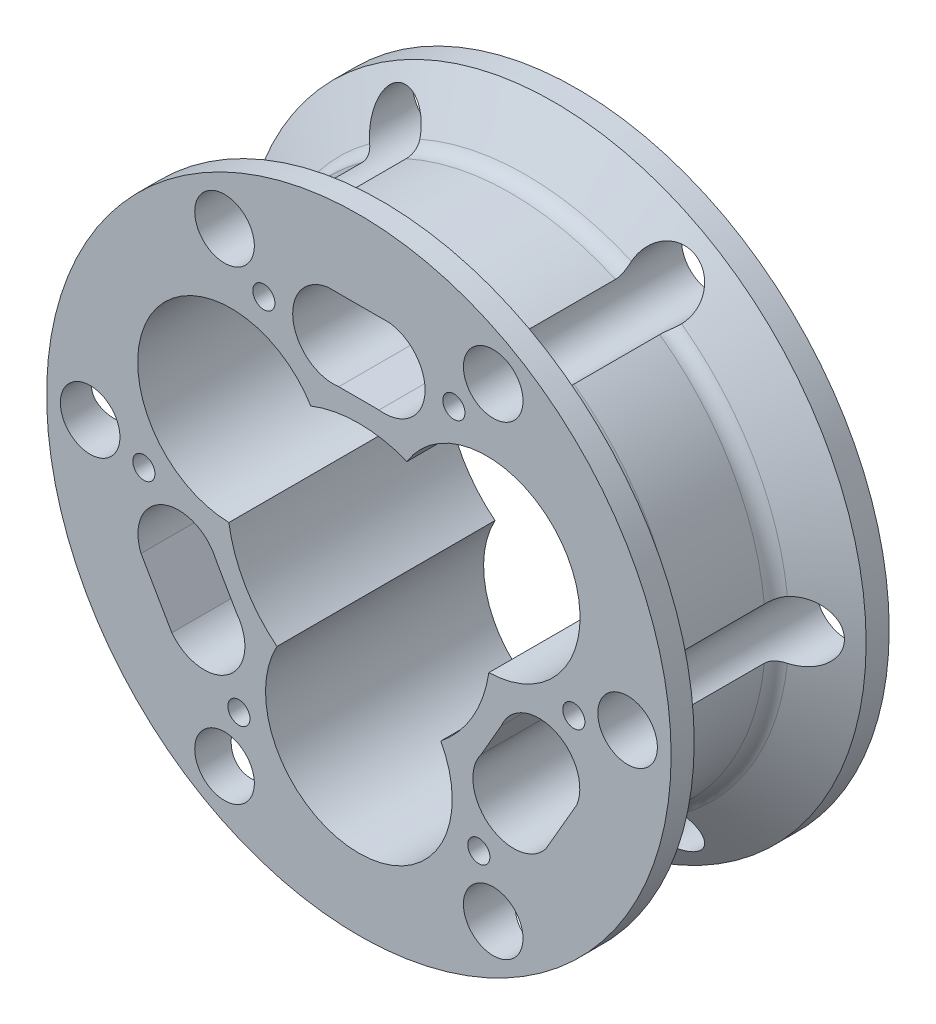
SolidWorks part; units mm, degrees
ref_plane "Front Plane" through (0, 0, 0) normal (0, 0, 1) x (1, 0, 0)
ref_plane "Top Plane" through (0, 0, 0) normal (0, 1, 0) x (1, 0, 0)
ref_plane "Right Plane" through (0, 0, 0) normal (1, 0, 0) x (0, 0, -1)
sketch "Sketch1" plane through (0, 0, 0) normal (0, 1, 0) x (1, 0, 0)
  line L0 (42.9895, 30.0228) -> (0, 30.0228)
  line L1 (0, 30.0228) -> (0, 0)
  line L2 (0, 0) -> (42.9895, 0)
  line L3 (42.9895, 0) -> (42.9895, 3.175)
  line L4 (42.9895, 3.175) -> (35.0774, 7.7431)
  line L5 (35.0774, 7.7431) -> (35.0774, 22.2797)
  line L6 (35.0774, 22.2797) -> (42.9895, 26.8478)
  line L7 (42.9895, 26.8478) -> (42.9895, 30.0228)
  line L8 (0, 30.0228) -> (0, 0) construction
revolve "Revolve1" add sketch "Sketch1" angle 360 about L8 reverse direction yes
sketch "Sketch2" plane through (0, 0, 0) normal (0, 0, 1) x (1, 0, 0)
  line L0 (25.7518, -19.7601) -> (29.9887, -12.4217)
  line L1 (19.6275, -8.13) -> (16.8546, -12.933)
  arc A0 (16.8546, -12.933) -> (25.7518, -19.7601) centre (21.3032, -16.3465) ccw
  arc A1 (29.9887, -12.4217) -> (19.6275, -8.13) centre (24.8081, -10.2759) ccw
extrude "Cut-Extrude1" cut sketch "Sketch2" against normal through all
sketch "Sketch3" plane through (0, 0, 0) normal (0, 0, 1) x (1, 0, 0)
  line L0 (-29.9887, -12.4217) -> (-25.7518, -19.7601)
  line L1 (-16.8546, -12.933) -> (-19.6275, -8.13)
  arc A0 (-19.6275, -8.13) -> (-29.9887, -12.4217) centre (-24.8081, -10.2759) ccw
  arc A1 (-25.7518, -19.7601) -> (-16.8546, -12.933) centre (-21.3032, -16.3465) ccw
extrude "Cut-Extrude2" cut sketch "Sketch3" against normal through all
sketch "Sketch4" plane through (0, 0, -30.0228) normal (0, 0, -1) x (-1, 0, 0)
  line L0 (-2.773, 21.0629) -> (2.773, 21.0629)
  line L1 (4.2368, 32.1818) -> (-4.2368, 32.1818)
  arc A0 (-4.2368, 32.1818) -> (-2.773, 21.0629) centre (-3.5049, 26.6224) ccw
  arc A1 (2.773, 21.0629) -> (4.2368, 32.1818) centre (3.5049, 26.6224) ccw
extrude "Cut-Extrude3" cut sketch "Sketch4" against normal through all
hole_wizard "Hole1" positions "Sketch6" profile "Sketch5" legacy
sketch "Sketch6" plane through (0, 0, -30.0228) normal (0, 0, -1) x (-1, 0, 0)
  point P0 (0, 0)
sketch "Sketch5" plane through (0, 0, -30.0228) normal (1, 0, 0) x (0, 1, 0)
  line L0 (0, 0) -> (0, 30.0228)
  line L1 (0, 30.0228) -> (18.0975, 30.0228)
  line L2 (18.0975, 30.0228) -> (18.0975, 0)
  line L3 (18.0975, 0) -> (0, 0)
  line L4 (0, 110) -> (0, -10) construction
  dimension "Diameter" = 36.195
  dimension "Depth" = 30.0228
hole_wizard "#31 (0.12) Diameter Hole1" positions "Sketch8" profile "Sketch7" hole size "#31" standard "ANSI Inch"
sketch "Sketch8" plane through (0, 0, 0) normal (0, 0, 1) x (1, 0, 0)
  point P0 (13.0812, 26.6224)
  point P1 (-13.0812, 26.6224)
  point P2 (-29.5963, -1.9825)
  point P3 (-16.515, -24.6399)
  point P4 (16.515, -24.6399)
  point P5 (29.5963, -1.9825)
sketch "Sketch7" plane through (13.0812, 26.6224, 0) normal (1, 0, 0) x (0, -1, 0)
  line L0 (0, 0) -> (0, 30.0228)
  line L1 (0, 30.0228) -> (1.524, 30.0228)
  line L2 (1.524, 30.0228) -> (1.524, 0)
  line L5 (1.524, 0) -> (0, 0)
  line L11 (0, -6.35) -> (0, 107.95) construction
  dimension "Thru Hole Dia." = 3.048
  dimension "Thru Hole Depth" = 30.0228
hole_wizard "P (0.323) Diameter Hole1" positions "Sketch10" profile "Sketch9" hole size "P" standard "ANSI Inch"
sketch "Sketch10" plane through (0, 0, -30.0228) normal (0, 0, -1) x (-1, 0, 0)
  point P0 (-36.9951, 0)
  point P1 (-18.4975, 32.0387)
  point P2 (18.4976, 32.0387)
  point P3 (36.9951, 0)
  point P4 (18.4975, -32.0387)
  point P5 (-18.4976, -32.0387)
sketch "Sketch9" plane through (36.9951, 0, -30.0228) normal (1, 0, 0) x (0, 1, 0)
  line L0 (0, 0) -> (0, 30.0228)
  line L1 (0, 30.0228) -> (4.1021, 30.0228)
  line L2 (4.1021, 30.0228) -> (4.1021, 0)
  line L5 (4.1021, 0) -> (0, 0)
  line L11 (0, -6.35) -> (0, 107.95) construction
  dimension "Thru Hole Dia." = 8.2042
  dimension "Thru Hole Depth" = 30.0228
hole_wizard "Hole2" positions "Sketch12" profile "Sketch11" legacy
sketch "Sketch12" plane through (0, 0, -30.0228) normal (0, 0, -1) x (-1, 0, 0)
  point P0 (0, -20.32)
  point P1 (17.5976, 10.16)
  point P2 (-17.5976, 10.16)
sketch "Sketch11" plane through (0, -20.32, -30.0228) normal (1, 0, 0) x (0, 1, 0)
  line L0 (0, 0) -> (0, 30.0228)
  line L1 (0, 30.0228) -> (12.8524, 30.0228)
  line L2 (12.8524, 30.0228) -> (12.8524, 0)
  line L3 (12.8524, 0) -> (0, 0)
  line L4 (0, 110) -> (0, -10) construction
  dimension "Diameter" = 25.7048
  dimension "Depth" = 30.0228
fillet "Fillet1" radius 2.3622 12 edges at (-30.3779, 17.5387, -22.2797) (30.3779, 17.5387, -22.2797) (0, 35.0774, -22.2797) (30.3779, -17.5387, -22.2797) (-30.3779, 17.5387, -7.7431) (0, -35.0774, -7.7431) (0, 35.0774, -7.7431) (0, -35.0774, -22.2797) (30.3779, 17.5387, -7.7431) (-30.3779, -17.5387, -7.7431) (30.3779, -17.5387, -7.7431) (-30.3779, -17.5387, -22.2797) tangent propagation no
